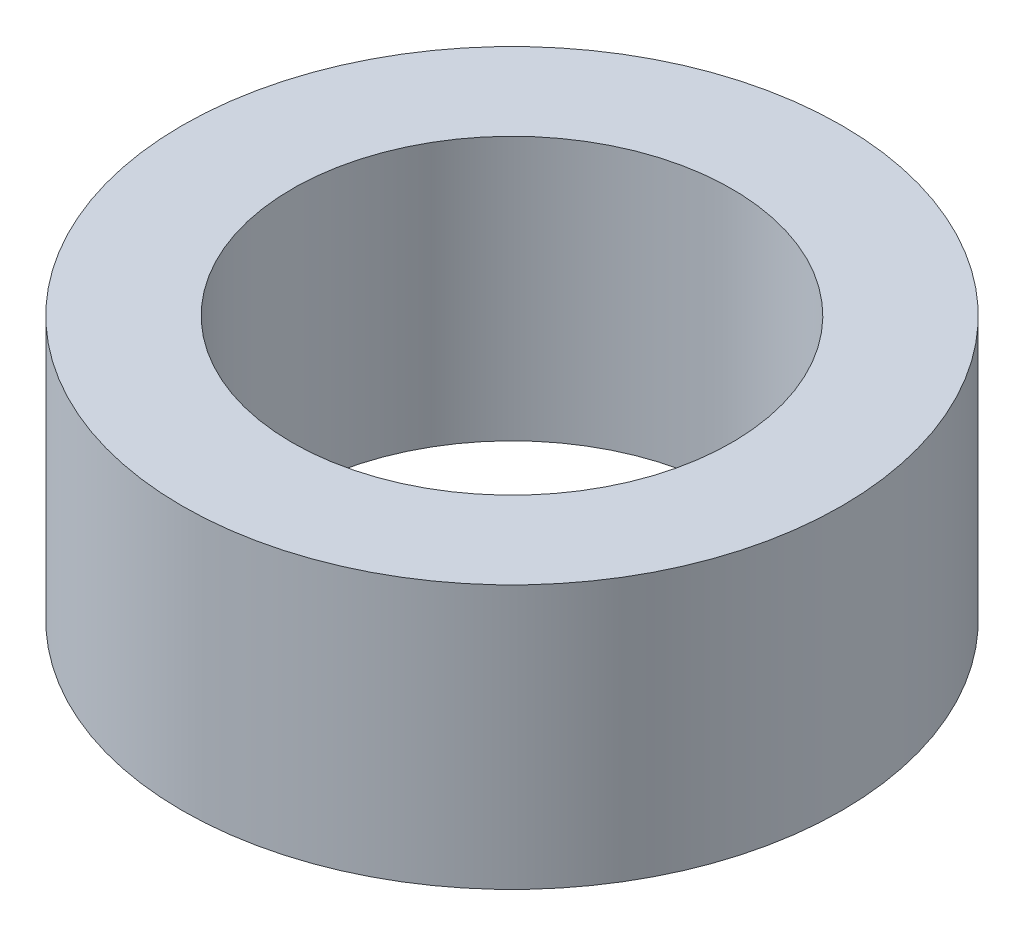
SolidWorks part; units mm, degrees
ref_plane "Front Plane" through (0, 0, 0) normal (0, 0, 1) x (1, 0, 0)
ref_plane "Top Plane" through (0, 0, 0) normal (0, 1, 0) x (1, 0, 0)
ref_plane "Right Plane" through (0, 0, 0) normal (1, 0, 0) x (0, 0, -1)
sketch "Sketch1" plane through (0, 0, 0) normal (0, 1, 0) x (1, 0, 0)
  circle A0 centre (0, 0) radius 22.5
  dimension "FLANGE_OD" = 45
extrude "Boss-Extrude1" add sketch "Sketch1" along normal blind 18
sketch "Sketch2" plane through (0, 0, 0) normal (0, 1, 0) x (1, 0, 0)
  circle A0 centre (0, 0) radius 15
  dimension "BORE_D" = 30
extrude "Cut-Extrude1" cut sketch "Sketch2" along normal through all
sketch "Sketch3" plane through (0, 18, 0) normal (0, 1, 0) x (1, 0, 0)
  circle A0 centre (0, 0) radius 9.6471 construction
  circle A1 centre (-9.6471, 0) radius 1.5
  dimension "BOLT_D" = 3
  dimension "BOLT_PCD" = 19.2942
extrude "Cut-Extrude2" cut sketch "Sketch3" against normal blind 13.1793 rebuild error yes
pattern_circular "CirPattern1" count 5 over 360 rebuild error yes
